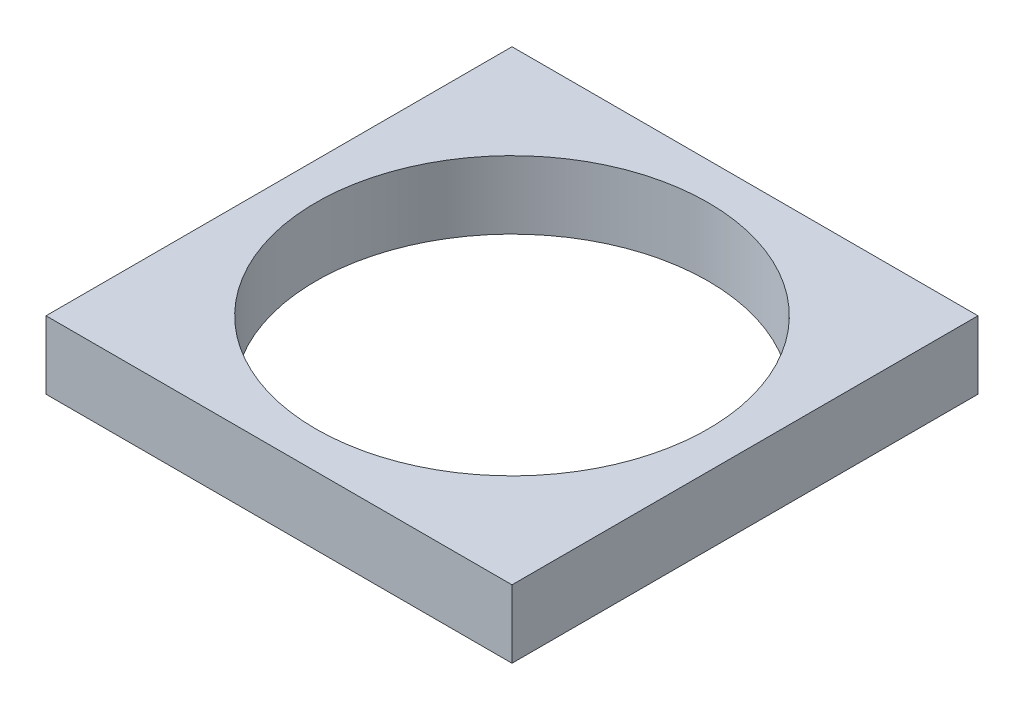
SolidWorks part; units mm, degrees
ref_plane "Front Plane" through (0, 0, 0) normal (0, 0, 1) x (1, 0, 0)
ref_plane "Top Plane" through (0, 0, 0) normal (0, 1, 0) x (1, 0, 0)
ref_plane "Right Plane" through (0, 0, 0) normal (1, 0, 0) x (0, 0, -1)
sketch "Sketch1" plane through (0, 0, 0) normal (0, 1, 0) x (1, 0, 0)
  line L1 (-76.2, -76.2) -> (76.2, -76.2)
  line L2 (-76.2, -76.2) -> (-76.2, 76.2)
  line L3 (-76.2, 76.2) -> (76.2, 76.2)
  line L4 (76.2, -76.2) -> (76.2, 76.2)
  line L5 (-76.2, -76.2) -> (76.2, 76.2) construction
  line L6 (-76.2, 76.2) -> (76.2, -76.2) construction
  circle A0 centre (0, 0) radius 64.135
  dimension "D1" = 128.27
  dimension "D2" = 152.4
  dimension "D3" = 152.4
extrude "Boss-Extrude1" add sketch "Sketch1" along normal blind 22.225
